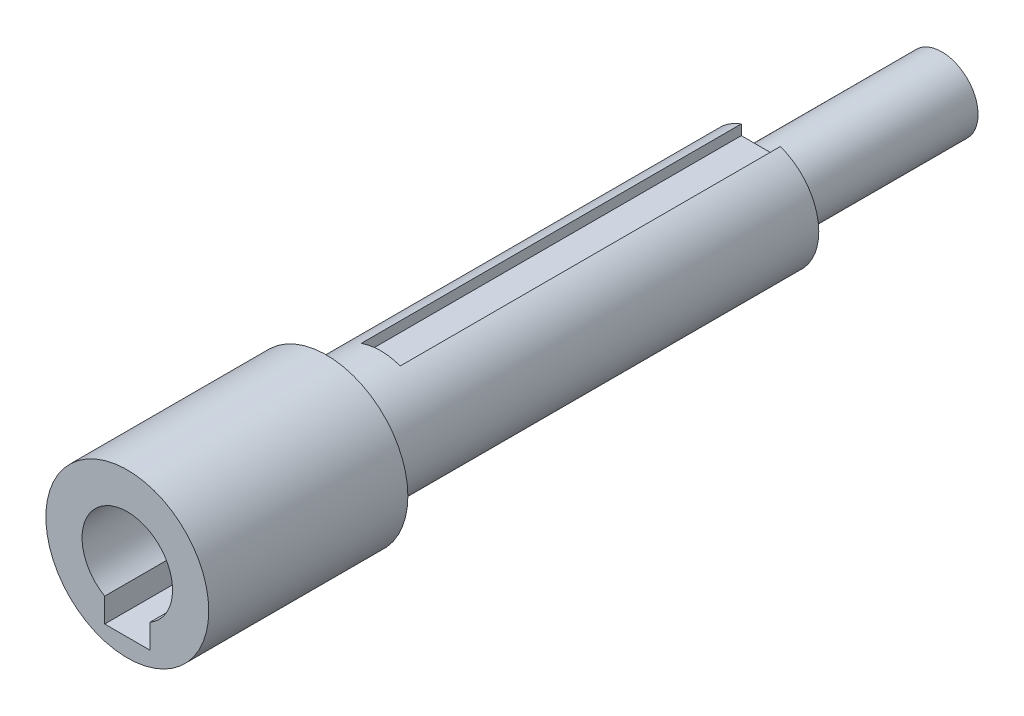
SolidWorks part; units mm, degrees
ref_plane "Front Plane" through (0, 0, 0) normal (0, 0, 1) x (1, 0, 0)
ref_plane "Top Plane" through (0, 0, 0) normal (0, 1, 0) x (1, 0, 0)
ref_plane "Right Plane" through (0, 0, 0) normal (1, 0, 0) x (0, 0, -1)
sketch "Sketch1" plane through (0, 0, 0) normal (0, 0, 1) x (1, 0, 0)
  circle A0 centre (0, 0) radius 5
  circle A1 centre (0, 0) radius 9
  dimension "D1" = 18
  dimension "D2" = 10
extrude "Boss-Extrude1" add sketch "Sketch1" along normal blind 20
sketch "Sketch3" plane through (0, 0, 0) normal (0, 0, -1) x (-1, 0, 0)
  circle A0 centre (0, 0) radius 6.4
  dimension "D1" = 12.8
extrude "Boss-Extrude2" add sketch "Sketch3" along normal blind 50
sketch "Sketch6" plane through (0, 0, 20) normal (0, 0, 1) x (1, 0, 0)
  line L0 (0, 0) -> (7, 0) construction
  line L1 (7, 1.025) -> (7, -1.025)
  point P6 (7, 0)
  dimension "D2" = 7
  dimension "D1" = 2.05
sketch "Sketch8" plane through (0, 0, 20) normal (0, 0, 1) x (1, 0, 0)
  line L0 (0, 0) -> (0, -5) construction
  line L1 (0, -5) -> (0, -7) construction
  line L2 (0, -7) -> (2.5, -7)
  line L3 (0, -7) -> (-2.5, -7)
  line L4 (-2.5, -7) -> (-2.5, -4.3301)
  line L5 (-2.5, -4.3301) -> (2.5, -4.3301)
  line L6 (2.5, -4.3301) -> (2.5, -7)
  circle A0 centre (0, 0) radius 5 construction
extrude "Cut-Extrude2" cut sketch "Sketch8" against normal blind 16
extrude "Boss-Extrude3" add sketch "Sketch1<3>" against normal blind 2 contours A1
sketch "Sketch1<3>" plane through (0, 0, 0) normal (0, 0, 1) x (1, 0, 0) same geometry as "Sketch1"
extrude "Boss-Extrude4" add sketch "Sketch1<4>" along normal blind 2 contours A0
sketch "Sketch1<4>" plane through (0, 0, 0) normal (0, 0, 1) x (1, 0, 0) same geometry as "Sketch1"
sketch "Sketch9" plane through (0, 0, -50) normal (0, 0, -1) x (-1, 0, 0)
  line L0 (0, 0) -> (0, 6.4) construction
  line L1 (0, 6.4) -> (0, 4.9)
  line L2 (0, 4.9) -> (2.16, 4.9)
  line L3 (0, 4.9) -> (-2.16, 4.9)
  line L4 (2.16, 4.9) -> (2.16, 6.0245)
  line L5 (2.16, 6.0245) -> (0.7433, 7.4412)
  line L6 (0.7433, 7.4412) -> (-1.7182, 7.4412)
  line L7 (-1.7182, 7.4412) -> (-2.16, 6.0245)
  line L8 (-2.16, 6.0245) -> (-2.16, 4.9)
  circle A0 centre (0, 0) radius 6.4 construction
  circle A1 centre (0, 0) radius 6.4 construction
  dimension "D1" = 1.5
extrude "Cut-Extrude3" cut sketch "Sketch9" against normal blind 42 contours L2 L4 L5 L6 L7 L8 L3
sketch "Sketch10" plane through (0, 0, -50) normal (0, 0, -1) x (-1, 0, 0)
  circle A0 centre (0, 0) radius 4
extrude "Boss-Extrude5" add sketch "Sketch10" along normal blind 20
